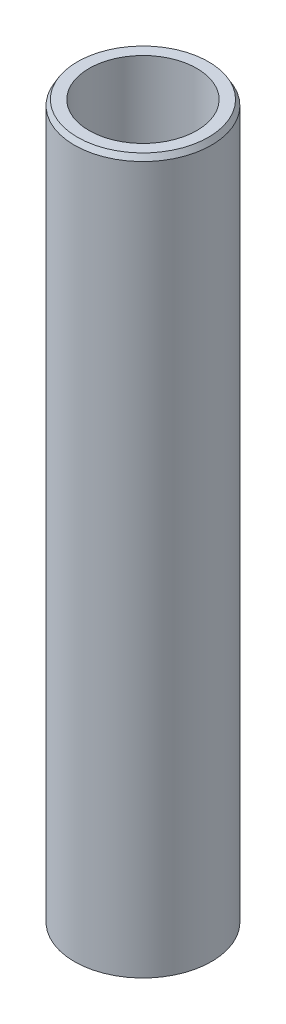
SolidWorks part; units mm, degrees
ref_plane "Front Plane" through (0, 0, 0) normal (0, 0, 1) x (1, 0, 0)
ref_plane "Top Plane" through (0, 0, 0) normal (0, 1, 0) x (1, 0, 0)
ref_plane "Right Plane" through (0, 0, 0) normal (1, 0, 0) x (0, 0, -1)
sketch "Sketch1" plane through (0, 0, 0) normal (0, 1, 0) x (1, 0, 0)
  circle A0 centre (0, 0) radius 57.5
  dimension "SHAFT_OD" = 115
extrude "Boss-Extrude1" add sketch "Sketch1" along normal blind 600
sketch "Sketch2" plane through (0, 0, 0) normal (0, 1, 0) x (1, 0, 0)
  circle A0 centre (0, 0) radius 45.1914
  dimension "BORE_D" = 90.3829
extrude "Cut-Extrude1" cut sketch "Sketch2" along normal through all
chamfer "Chamfer1" distance 4.4588 angle 30 2 edges at (0, 600, 57.5) (0, 0, 57.5) first distance on face at (0, 600, 57.5) first distance on face at (0, 0, 45.1914)
